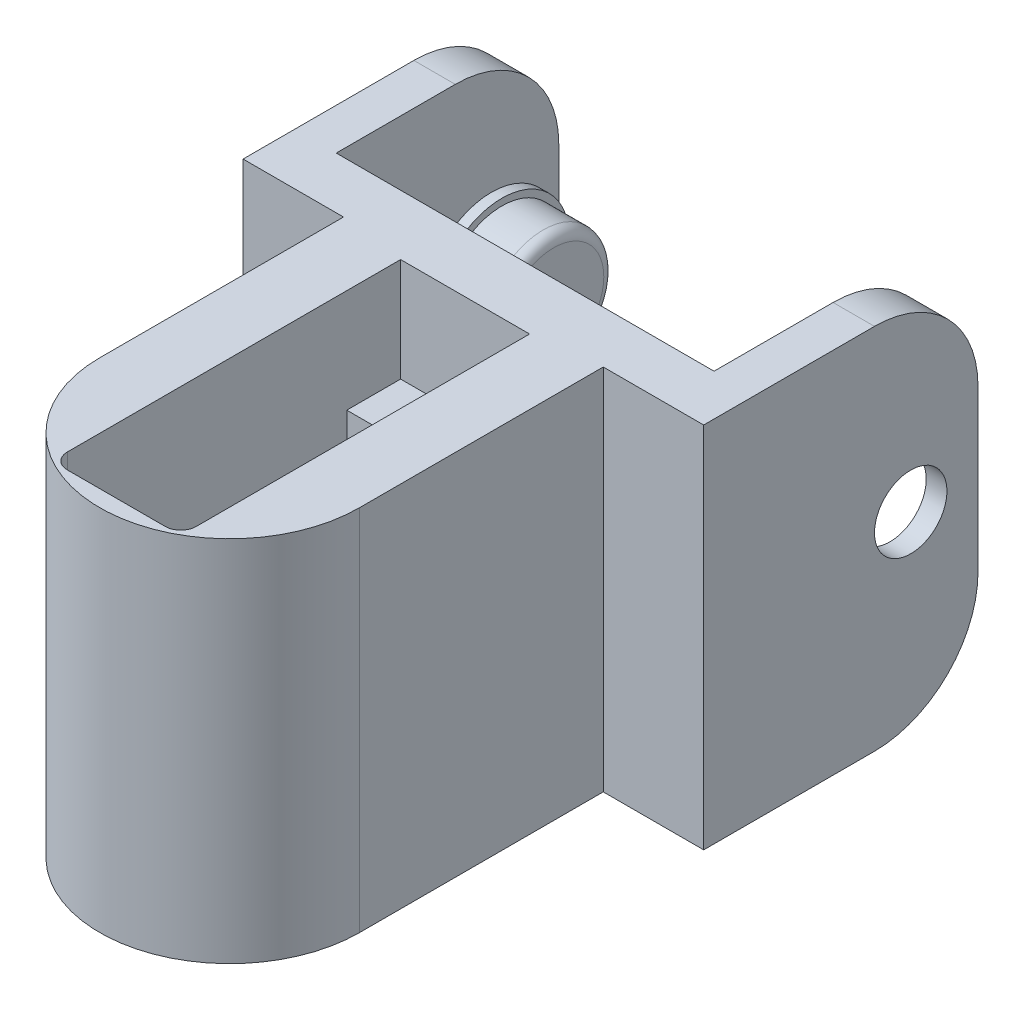
SolidWorks part; units mm, degrees
ref_plane "Front Plane" through (0, 0, 0) normal (0, 0, 1) x (1, 0, 0)
ref_plane "Top Plane" through (0, 0, 0) normal (0, 1, 0) x (1, 0, 0)
ref_plane "Right Plane" through (0, 0, 0) normal (1, 0, 0) x (0, 0, -1)
sketch "Sketch4" plane through (0, 0, 0) normal (0, 0, 1) x (1, 0, 0)
  line L1 (-6.23, -9.975) -> (6.23, -9.975)
  line L2 (-6.23, -9.975) -> (-6.23, 7.275)
  line L3 (-6.23, 7.275) -> (6.23, 7.275)
  line L4 (6.23, -9.975) -> (6.23, 7.275)
  point P4 (0, 7.275)
  dimension "D1" = 12.46
  dimension "D2" = 17.25
  dimension "D3" = 9.975
extrude "Boss-Extrude3" add sketch "Sketch4" along normal blind 6
sketch "Sketch8" plane through (0, -9.975, 0) normal (0, -1, 0) x (-1, 0, 0)
  circle A0 centre (0, -23.55) radius 12.5468
  circle A1 centre (0, -23.55) radius 11.15
  dimension "D1" = 22.3
  dimension "D2" = 23.55
extrude "Boss-Extrude6" add sketch "Sketch8" along normal blind 8.3 and the other way up to surface (17.25 mm away) other way up to face at (0, 7.275, 3)
sketch "Sketch5" plane through (0, 7.275, 0) normal (0, 1, 0) x (1, 0, 0)
  line L8 (12.5468, -23.55) -> (12.5468, 0)
  line L9 (12.5468, 0) -> (6.23, 0)
  line L10 (-12.5468, -23.55) -> (-12.5468, 0)
  line L11 (-12.5468, 0) -> (-6.23, 0)
  line L12 (-6.23, 0) -> (-6.23, -29.7)
  line L14 (6.23, -29.7) -> (6.23, 0)
  line L15 (-6.23, -29.7) -> (6.23, -29.7)
  line L16 (6.23, -6) -> (-6.23, -6) construction
  circle A0 centre (0, -23.55) radius 12.5468 construction
  arc A1 (-12.5468, -23.55) -> (12.5468, -23.55) centre (0, -23.55) ccw
  dimension "D1" = 23.7
  dimension "D2" = 23.55
extrude "Boss-Extrude4" add sketch "Sketch5" against normal up to surface (17.25 mm away) up to face at (0, -9.975, 3)
sketch "Sketch6" plane through (0, 7.275, 0) normal (0, 1, 0) x (1, 0, 0)
  line L0 (6.23, -6) -> (-6.23, -6) construction
  line L3 (6.23, -29.7) -> (-6.23, -29.7) construction
  circle A0 centre (0, -3.6) radius 0.75
  circle A1 centre (0, -32.1) radius 0.75
  dimension "D1" = 1.5
  dimension "D3" = 1.5
  dimension "D2" = 2.4
  dimension "D4" = 2.4
extrude "Cut-Extrude1" cut sketch "Sketch6" against normal blind 5
chamfer "Chamfer1" distance 0.5 angle 60 2 edges at (0, 7.275, 4.35) (0, 7.275, 32.85) first distance on face at (0, 7.275, 4.35)
sketch "Sketch10" plane through (0, 7.275, 0) normal (0, 1, 0) x (1, 0, 0)
  line L1 (-6.23, -6) -> (6.23, -6)
  line L2 (-6.23, -6) -> (-6.23, -29.7)
  line L3 (-6.23, -29.7) -> (6.23, -29.7)
  line L4 (6.23, -6) -> (6.23, -29.7)
extrude "Cut-Extrude3" cut sketch "Sketch10" against normal up to surface (17.25 mm away) up to face at (0, -9.975, 27.1007)
ref_plane "Plane1" through (0, 0, 36.0968) normal (0, 0, 1) x (1, 0, 0)
sketch "Sketch13" plane through (0, -18.275, 0) normal (0, -1, 0) x (1, 0, 0)
  line L0 (-12.5468, 23.55) -> (-12.5468, 0)
  line L1 (-12.5468, 0) -> (12.5468, 0)
  line L2 (12.5468, 0) -> (12.5468, 23.55)
  arc A0 (-12.5468, 23.55) -> (12.5468, 23.55) centre (0, 23.55) ccw
  point P3 (0, 0)
extrude "Boss-Extrude7" add sketch "Sketch13" against normal up to surface (8.3 mm away) up to face at (0, -9.975, 27.1007)
sketch "Sketch15" plane through (0, 7.275, 0) normal (0, 1, 0) x (1, 0, 0)
  line L0 (-12.5468, 0) -> (12.5468, 0)
  line L1 (12.5468, 0) -> (12.5468, -23.55)
  line L2 (-12.5468, 0) -> (-12.5468, -23.55)
  line L3 (6.23, -6) -> (6.23, -29.7) construction
  line L4 (-6.23, -0.8) -> (6.23, -0.8)
  line L5 (-6.23, -0.8) -> (-6.23, -33)
  line L6 (-4.73, -34.5) -> (4.73, -34.5)
  line L7 (6.23, -0.8) -> (6.23, -33)
  arc A0 (-12.5468, -23.55) -> (12.5468, -23.55) centre (0, -23.55) ccw
  circle A1 centre (0, -3.6) radius 0.75 construction
  arc A2 (4.73, -34.5) -> (6.23, -33) centre (4.73, -33) ccw
  arc A3 (-6.23, -33) -> (-4.73, -34.5) centre (-4.73, -33) ccw
  point P15 (0, -0.8)
  dimension "D1" = 0.8
  dimension "D3" = 1.5
  dimension "D2" = 2.8
  dimension "D4" = 0
  dimension "D5" = 34.5
extrude "Boss-Extrude9" add sketch "Sketch15" along normal blind 10
sketch "Sketch20" plane through (0, -18.275, 0) normal (0, -1, 0) x (1, 0, 0)
  circle A0 centre (0, 23.55) radius 7.15
  circle A1 centre (0, 23.55) radius 11.15
  circle A2 centre (0, 23.55) radius 11.15 construction
  dimension "D1" = 14.3
extrude "Boss-Extrude11" add sketch "Sketch20" against normal up to surface (8.3 mm away) up to face at (0, -9.975, 27.1007)
sketch "Sketch21" plane through (0, -18.275, 0) normal (0, -1, 0) x (1, 0, 0)
  circle A0 centre (0, 23.55) radius 7.15
  circle A1 centre (0, 23.55) radius 10.15
  circle A2 centre (0, 23.55) radius 7.15 construction
  dimension "D1" = 20.3
extrude "Cut-Extrude7" cut sketch "Sketch21" against normal blind 1.3
sketch "Sketch11" plane through (0, 0, 29.7) normal (0, 0, 1) x (1, 0, 0)
  line L1 (-5, -9.975) -> (5, -9.975)
  line L2 (-5, -9.975) -> (-5, -11.975)
  line L3 (-5, -11.975) -> (5, -11.975)
  line L4 (5, -9.975) -> (5, -11.975)
  line L5 (-3.6469, -9.975) -> (3.6469, -9.975) construction
  point P4 (0, -9.975)
  dimension "D1" = 0
  dimension "D2" = 10
  dimension "D3" = 2
extrude "Cut-Extrude4" cut sketch "Sketch11" against normal up to surface (23.7 mm away) up to face at (0, -1.35, 6)
sketch "Sketch17" plane through (0, 17.275, 0) normal (0, 1, 0) x (1, 0, 0)
  line L0 (22.25, 26.5) -> (22.25, 0)
  line L1 (22.25, 0) -> (-22.25, 0)
  line L2 (-22.25, 0) -> (-22.25, 26.5)
  line L3 (-22.25, 26.5) -> (-18.25, 26.5)
  line L4 (-18.25, 26.5) -> (-18.25, 5)
  line L5 (-18.25, 5) -> (18.25, 5)
  line L6 (18.25, 5) -> (18.25, 26.5)
  line L7 (18.25, 26.5) -> (22.25, 26.5)
  point P2 (0, 5)
  point P10 (0, 0)
  dimension "D1" = 4
  dimension "D2" = 36.5
  dimension "D3" = 0
  dimension "D4" = 26.5
  dimension "D5" = 5
extrude "Boss-Extrude10" add sketch "Sketch17" against normal up to surface (35.55 mm away) up to face at (0, -18.275, 13.4)
sketch "Sketch18" plane through (18.25, 0, 0) normal (-1, 0, 0) x (0, 0, 1)
  line L0 (-26.5, -18.275) -> (-26.5, 17.275) construction
  line L1 (-26.5, 5.2191) -> (-5, 5.2191)
  line L2 (-26.5, 5.2191) -> (-26.5, -6.2191)
  line L3 (-26.5, -6.2191) -> (-5, -6.2191)
  line L4 (-5, 5.2191) -> (-5, -6.2191)
  line L5 (-5, -18.275) -> (-5, 17.275) construction
  point P6 (-26.5, -0.5)
  point P7 (-26.5, -0.5)
  dimension "D1" = 0
extrude "Cut-Extrude5" cut sketch "Sketch18" against normal blind 2
sketch "Sketch19" plane through (20.25, 0, 0) normal (-1, 0, 0) x (0, 0, 1)
  line L0 (-26.5, -18.275) -> (-26.5, 17.275) construction
  circle A0 centre (-20, 0) radius 3.5
  dimension "D1" = 7
  dimension "D2" = 6.5
extrude "Cut-Extrude6" cut sketch "Sketch19" against normal through all both and the other way through all
fillet "Fillet1" radius 10 4 edges at (20.25, -18.275, -26.5) (20.25, 17.275, -26.5) (-20.25, 17.275, -26.5) (-20.25, -18.275, -26.5)
ref_plane "Plane2" through (0, 0, 0) normal (1, 0, 0) x (0, 0, -1)
ref_plane "Plane3" through (0, -0.5, 0) normal (0, -1, 0) x (-1, 0, 0)
sketch "Sketch22" plane through (-22.25, 0, 0) normal (-1, 0, 0) x (0, 0, 1)
  circle A0 centre (-20, 0) radius 6.5
  dimension "D1" = 13
extrude "Boss-Extrude12" add sketch "Sketch22" against normal blind 5
sketch "Sketch23" plane through (-17.25, 0, 0) normal (1, 0, 0) x (0, 0, -1)
  circle A0 centre (20, 0) radius 5.85
  dimension "D1" = 11.7
extrude "Boss-Extrude13" add sketch "Sketch23" along normal blind 5
fillet "Fillet2" radius 1 1 edges at (-12.25, 0, -25.85)
sketch "Sketch25" plane through (0, -18.275, 0) normal (0, -1, 0) x (1, 0, 0)
  line L0 (6.23, 20.0415) -> (6.23, 6) construction
  line L1 (-6.23, 6) -> (6.23, 6)
  line L2 (-6.23, 6) -> (-6.23, 11)
  line L3 (-6.23, 11) -> (6.23, 11)
  line L4 (6.23, 6) -> (6.23, 11)
  dimension "D1" = 5
extrude "Cut-Extrude8" cut sketch "Sketch25" against normal up to next
